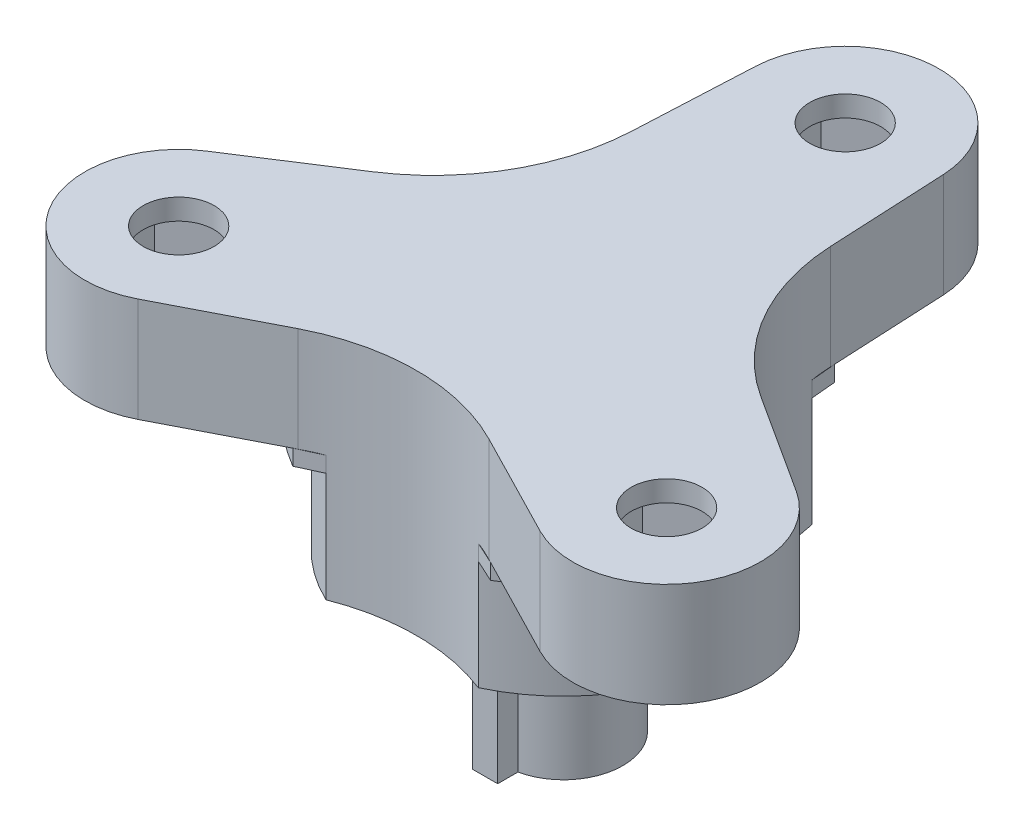
SolidWorks part; units mm, degrees
ref_plane "Ön Düzlem" through (0, 0, 0) normal (0, 0, 1) x (1, 0, 0)
ref_plane "Üst Düzlem" through (0, 0, 0) normal (0, 1, 0) x (1, 0, 0)
ref_plane "Sağ Düzlem" through (0, 0, 0) normal (1, 0, 0) x (0, 0, -1)
sketch "Sketch1" plane through (0, 0, 0) normal (0, 1, 0) x (1, 0, 0)
  line L0 (-4.4946, 13.7195) -> (-4.7723, 8.0342)
  line L1 (0, 13.5) -> (0, 0) construction
  line L2 (4.4946, 13.7195) -> (4.7723, 8.0342)
  line L3 (9.6341, -10.7522) -> (4.5717, -8.15)
  line L4 (14.1287, -2.9673) -> (9.3439, 0.1158)
  line L5 (-14.1287, -2.9673) -> (-9.3439, 0.1158)
  line L6 (-9.6341, -10.7522) -> (-4.5717, -8.15)
  circle A1 centre (0, 13.5) radius 1.7
  arc A3 (4.4946, 13.7195) -> (-4.4946, 13.7195) centre (0, 13.5) ccw
  circle A5 centre (0, 13.5) radius 4.5 construction
  circle A6 centre (11.6913, -6.75) radius 1.7
  arc A7 (9.6341, -10.7522) -> (14.1287, -2.9673) centre (11.6913, -6.75) ccw
  circle A8 centre (-11.6913, -6.75) radius 1.7
  arc A9 (-14.1287, -2.9673) -> (-9.6341, -10.7522) centre (-11.6913, -6.75) ccw
  circle A10 centre (0, 0) radius 5.8 construction
  arc A11 (-4.5717, -8.15) -> (4.5717, -8.15) centre (0, -17.0438) cw
  arc A12 (9.3439, 0.1158) -> (4.7723, 8.0342) centre (14.7604, 8.5219) cw
  arc A13 (-4.7723, 8.0342) -> (-9.3439, 0.1158) centre (-14.7604, 8.5219) cw
  point P27 (5.0229, 2.9)
  point P30 (0, 0)
  point P32 (-5.0229, 2.9)
  dimension "D2" = 3.4
  dimension "D3" = 11.6
  dimension "D7" = 10
  dimension "D4" = 4.5
  dimension "D1" = 13.5
  dimension "D6" = 3
extrude "Boss-Extrude1" add sketch "Sketch1" along normal blind 5
sketch "Sketch2" plane through (0, 5, 0) normal (0, 1, 0) x (1, 0, 0)
  line L0 (14.4413, -8.3377) -> (14.4413, -5.1623)
  line L1 (0, 16.6754) -> (-2.75, 15.0877)
  line L2 (-2.75, 15.0877) -> (-2.75, 11.9123)
  line L3 (-2.75, 11.9123) -> (0, 10.3246)
  line L4 (0, 10.3246) -> (2.75, 11.9123)
  line L5 (2.75, 11.9123) -> (2.75, 15.0877)
  line L6 (2.75, 15.0877) -> (0, 16.6754)
  line L7 (14.4413, -5.1623) -> (11.6913, -3.5746)
  line L8 (11.6913, -3.5746) -> (8.9413, -5.1623)
  line L9 (8.9413, -5.1623) -> (8.9413, -8.3377)
  line L10 (8.9413, -8.3377) -> (11.6913, -9.9254)
  line L11 (11.6913, -9.9254) -> (14.4413, -8.3377)
  line L12 (-14.4413, -8.3377) -> (-11.6913, -9.9254)
  line L13 (-11.6913, -9.9254) -> (-8.9413, -8.3377)
  line L14 (-8.9413, -8.3377) -> (-8.9413, -5.1623)
  line L15 (-8.9413, -5.1623) -> (-11.6913, -3.5746)
  line L16 (-11.6913, -3.5746) -> (-14.4413, -5.1623)
  line L17 (-14.4413, -5.1623) -> (-14.4413, -8.3377)
  circle A0 centre (0, 13.5) radius 2.75 construction
  point P24 (0, 0)
  dimension "D1" = 5.5
  dimension "D2" = 3
extrude "Cut-Extrude1" cut sketch "Sketch2" along normal blind 4 from surface starting at face at (0, 0, 0)
sketch "Sketch3" plane through (0, 0, 0) normal (0, -1, 0) x (1, 0, 0)
  circle A0 centre (0, 0) radius 2.5 construction
  dimension "D1" = 5
sketch "Sketch4" plane through (0, 0, 0) normal (0, -1, 0) x (1, 0, 0)
  arc A0 (-4.873, -7.0254) -> (4.873, -7.0254) centre (0, 0) ccw
  arc A1 (-3.6477, 7.7328) -> (-8.5207, -0.7074) centre (0, 0) ccw
  arc A2 (8.5207, -0.7074) -> (3.6477, 7.7328) centre (0, 0) ccw
  arc A3 (-4.7723, -8.0342) -> (-9.3439, -0.1158) centre (-14.7604, -8.5219) ccw construction
  arc A4 (-4.5717, 8.15) -> (4.5717, 8.15) centre (0, 17.0438) ccw construction
  arc A5 (9.3439, -0.1158) -> (4.7723, -8.0342) centre (14.7604, -8.5219) ccw construction
  arc A6 (-4.873, -7.0254) -> (-8.5207, -0.7074) centre (-14.7604, -8.5219) ccw
  arc A7 (-3.6477, 7.7328) -> (3.6477, 7.7328) centre (0, 17.0438) ccw
  arc A8 (8.5207, -0.7074) -> (4.873, -7.0254) centre (14.7604, -8.5219) ccw
  dimension "D1" = 17.1
extrude "Boss-Extrude2" add sketch "Sketch4" along normal blind 6
sketch "Sketch5" plane through (0, 0, 0) normal (0, -1, 0) x (1, 0, 0)
  line L0 (-9.6341, 10.7522) -> (-4.5717, 8.15) construction
  line L1 (-9.3439, -0.1158) -> (-14.1287, 2.9673) construction
  line L2 (-9.5, -0.0152) -> (-8.5207, -0.7074)
  line L3 (-4.7368, 8.2349) -> (-3.6477, 7.7328)
  line L4 (9.5, -0.0152) -> (8.5207, -0.7074)
  line L5 (4.7368, 8.2349) -> (3.6477, 7.7328)
  line L6 (-4.7632, -8.2196) -> (-4.873, -7.0254)
  line L7 (4.7632, -8.2196) -> (4.873, -7.0254)
  arc A0 (-4.873, -7.0254) -> (4.873, -7.0254) centre (0, 0) ccw construction
  arc A1 (8.5207, -0.7074) -> (3.6477, 7.7328) centre (0, 0) ccw construction
  arc A2 (-3.6477, 7.7328) -> (-8.5207, -0.7074) centre (0, 0) ccw construction
  arc A3 (-4.873, -7.0254) -> (4.873, -7.0254) centre (0, 0) ccw
  arc A4 (8.5207, -0.7074) -> (3.6477, 7.7328) centre (0, 0) ccw
  arc A5 (-3.6477, 7.7328) -> (-8.5207, -0.7074) centre (0, 0) ccw
  arc A6 (-4.7368, 8.2349) -> (-9.5, -0.0152) centre (0, 0) ccw
  arc A7 (9.5, -0.0152) -> (4.7368, 8.2349) centre (0, 0) ccw
  arc A8 (-4.7632, -8.2196) -> (4.7632, -8.2196) centre (0, 0) ccw
  point P24 (0, 0)
  dimension "D1" = 9.5
extrude "Boss-Extrude3" add sketch "Sketch5" along normal blind 0.75
sketch "Sketch6" plane through (0, -6, 0) normal (0, -1, 0) x (1, 0, 0)
  line L0 (-0.75, 2.9047) -> (-0.75, 3.9047) construction
  line L1 (0.75, 2.9047) -> (0.75, 3.9047) construction
  line L2 (-0.75, 3.4047) -> (0.75, 3.4047) construction
  line L3 (-0.75, 3.9047) -> (0.75, 3.9047) construction
  line L4 (0.6, 2.7861) -> (0.6, 3.7547)
  line L5 (-0.6, 3.7547) -> (0.6, 3.7547)
  line L6 (-0.6, 2.7861) -> (-0.6, 3.7547)
  arc A0 (-0.75, 2.9047) -> (0.75, 2.9047) centre (0, 0) ccw construction
  arc A1 (-0.6, 2.7861) -> (0.6, 2.7861) centre (0, 0) ccw
  point P9 (0, 3.4047)
  dimension "D1" = 6
  dimension "D2" = 1.5
  dimension "D3" = 1
  dimension "D4" = 0.15
extrude "Boss-Extrude4" add sketch "Sketch6" along normal blind 7.5
sketch "Sketch7" plane through (0, -13.5, 0) normal (0, -1, 0) x (1, 0, 0)
  circle A2 centre (0, 0) radius 2.25
  dimension "D1" = 4.5
extrude "Cut-Extrude2" cut sketch "Sketch7" against normal blind 4.4
sketch "Sketch8" plane through (0, -9.1, 0) normal (0, -1, 0) x (1, 0, 0)
  circle A0 centre (0, 0) radius 1.95
  dimension "D1" = 3.9
extrude "Cut-Extrude3" cut sketch "Sketch8" against normal blind 5.5
